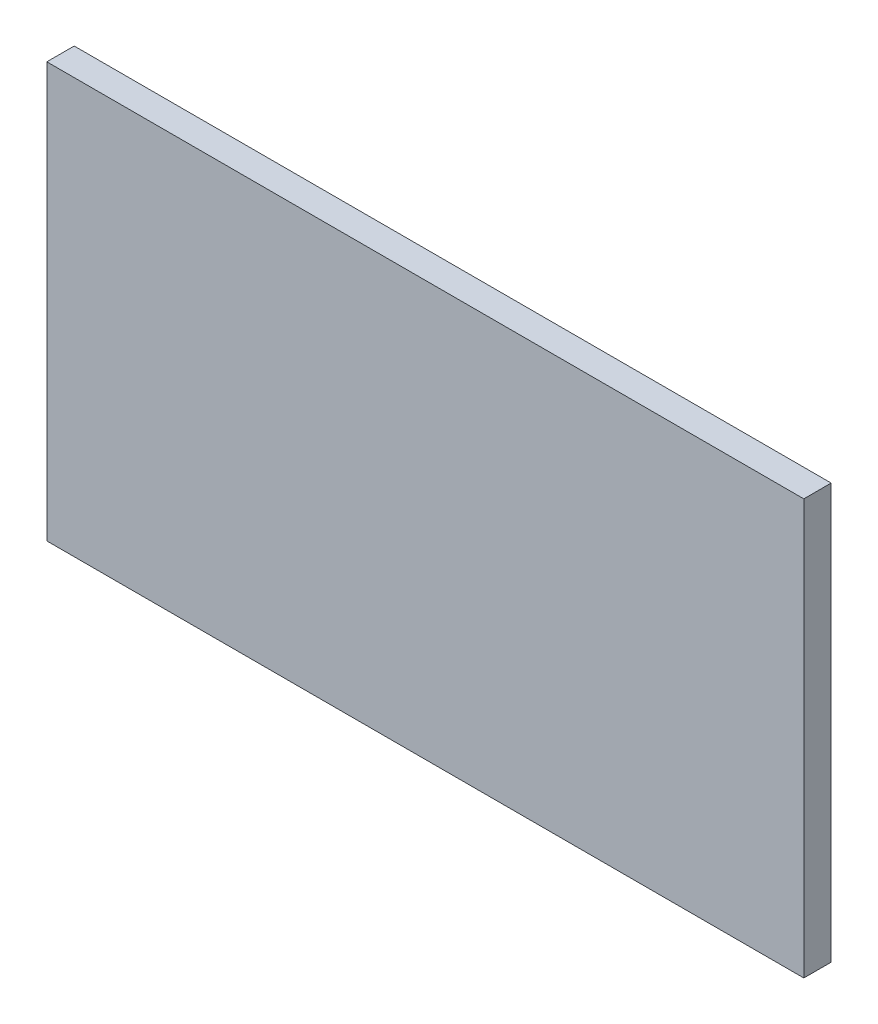
SolidWorks part; units mm, degrees
ref_plane "Front" through (0, 0, 0) normal (0, 0, 1) x (1, 0, 0)
ref_plane "Top" through (0, 0, 0) normal (0, 1, 0) x (1, 0, 0)
ref_plane "Right" through (0, 0, 0) normal (1, 0, 0) x (0, 0, -1)
sketch "Sketch1" plane through (0, 0, 0) normal (0, 0, 1) x (1, 0, 0)
  line L1 (0, 0) -> (41.5, 0)
  line L2 (0, 0) -> (0, 22.75)
  line L3 (0, 22.75) -> (41.5, 22.75)
  line L4 (41.5, 0) -> (41.5, 22.75)
  line L5 (5.5, 15.25) -> (9.5, 15.25)
  line L6 (5.5, 15.25) -> (5.5, 12.25)
  line L7 (5.5, 12.25) -> (9.5, 12.25)
  line L8 (9.5, 15.25) -> (9.5, 12.25)
  line L9 (19.75, 15) -> (24.5, 15)
  line L10 (19.75, 15) -> (19.75, 3)
  line L11 (19.75, 3) -> (24.5, 3)
  line L12 (24.5, 15) -> (24.5, 3)
  dimension "D1" = 22.75
  dimension "D2" = 41.5
  dimension "D3" = 5.5
  dimension "D4" = 19.75
  dimension "D5" = 7.5
  dimension "D6" = 4
  dimension "D7" = 3
  dimension "D8" = 4.75
  dimension "D9" = 12
  dimension "D10" = 7.75
extrude "Boss-Extrude1" add sketch "Sketch1" along normal blind 1.5 contours L3 L4 L1 L2
extrude "Boss-Extrude2" add sketch "Sketch1<3>" against normal blind 2 contours L12 L9 L10 L11 | L8 L5 L6 L7 region at (7.5, 13.75, 0) region at (22.125, 9, 0)
sketch "Sketch1<3>" plane through (0, 0, 0) normal (0, 0, 1) x (1, 0, 0) same geometry as "Sketch1"
